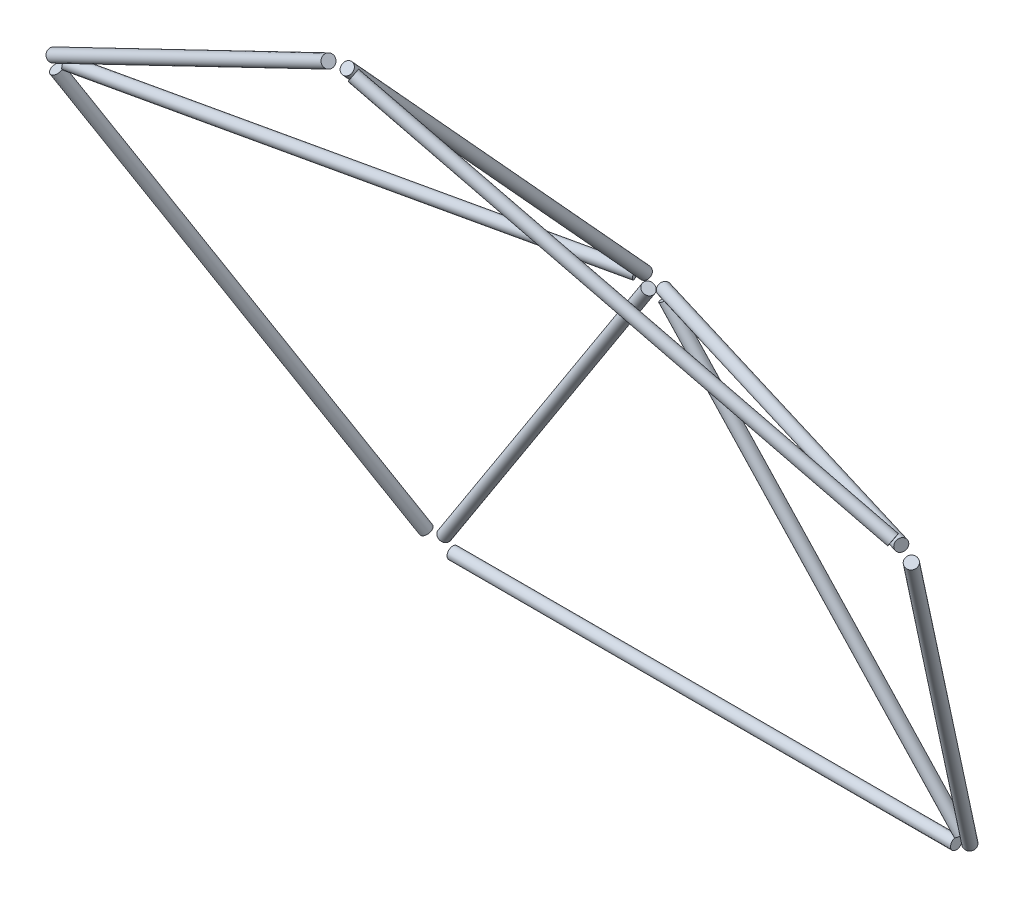
SolidWorks part; units mm, degrees
note: '?' marks a value the reader was unsure of.
ref_plane "Front Plane" through (0, 0, 0) normal (0, 0, 1) x (1, 0, 0)
ref_plane "Top Plane" through (0, 0, 0) normal (0, 1, 0) x (1, 0, 0)
ref_plane "Right Plane" through (0, 0, 0) normal (1, 0, 0) x (0, 0, -1)
sketch "Sketch1" plane through (0, 0, 0) normal (0, 1, 0) x (1, 0, 0)
  line L0 (178.7928, 134.6028) -> (72.7649, 211.6366)
  line L1 (182.0288, -132.2517) -> (225, 0) construction
  line L2 (225, 0) -> (182.0288, 132.2517) construction
  line L3 (182.0288, 132.2517) -> (69.5288, 213.9877) construction
  line L4 (69.5288, 213.9877) -> (-69.5288, 213.9877) construction
  line L5 (-69.5288, 213.9877) -> (-182.0288, 132.2517) construction
  line L6 (-182.0288, 132.2517) -> (-225, 0) construction
  line L7 (-225, 0) -> (-182.0288, -132.2517) construction
  line L8 (-182.0288, -132.2517) -> (-69.5288, -213.9877) construction
  line L9 (-69.5288, -213.9877) -> (69.5288, -213.9877) construction
  line L10 (69.5288, -213.9877) -> (182.0288, -132.2517) construction
  line L11 (112.5, 81.736) -> (69.5288, 213.9877) construction
  line L12 (69.5288, 213.9877) -> (-69.5288, 213.9877) construction
  line L13 (-69.5288, 213.9877) -> (-112.5, 81.736) construction
  line L14 (-112.5, 81.736) -> (0, 0) construction
  line L15 (0, 0) -> (112.5, 81.736) construction
  line L16 (0, 0) -> (-182.0288, -132.2517) construction
  line L17 (-69.5288, -213.9877) -> (69.5288, 213.9877) construction
  circle A0 centre (0, 0) radius 225 construction
  circle A1 centre (0, 0) radius 213.9877 construction
  circle A2 centre (0, 118.2895) radius 95.6982 construction
  point P16 (0, 225)
  point P24 (0, 213.9877)
  dimension "D1" = 450
  dimension "D2" = 4
  dimension "D3" = 4
sketch "Sketch5" plane through (0, 0, 0) normal (1, 0, 0) x (0, 0, -1)
  line L0 (0, 0) -> (118.2895, 191.3964)
  line L1 (118.2895, 191.3964) -> (213.9877, 0)
  line L2 (171.1902, 85.5951) -> (201.2461, 100.6231) construction
  line L3 (-49.7754, 154.1978) -> (144.5877, 34.0748) construction
  circle A0 centre (213.9877, 0) radius 213.9877 construction
  circle A1 centre (0, 0) radius 225 construction
  circle A2 centre (213.9877, 0) radius 95.6982 construction
  point P0 (213.9877, 0)
  point P8 (118.2895, 191.3964)
ref_plane "Plane1" through (0, 85.5951, -171.1902) normal (0, 0.4472, -0.8944) x (-1, 0, 0)
sketch "Sketch6" plane through (0, 85.5951, -171.1902) normal (0, 0.4472, -0.8944) x (-1, 0, 0)
  line L0 (-69.5288, -95.6982) -> (69.5288, -95.6982) construction
  line L1 (-69.5288, -95.6982) -> (69.5288, -95.6982)
  line L2 (-111.2639, 32.7492) -> (-70.7649, -91.894)
  line L3 (-69.5288, -95.6982) -> (69.5288, -95.6982)
  line L4 (69.5288, -95.6982) -> (112.5, 36.5535)
  line L5 (112.5, 36.5535) -> (0, 118.2895)
  line L6 (0, 118.2895) -> (-112.5, 36.5535)
  line L7 (-112.5, 36.5535) -> (-69.5288, -95.6982) construction
  circle A0 centre (0, 0) radius 95.6982 construction
  point P0 (0, 0)
  dimension "D1" = 4
  dimension "D2" = 4
ref_plane "Plane2" through (0, 100.6231, -201.2461) normal (0, 0.4472, -0.8944) x (-1, 0, 0)
sketch "Sketch7" plane through (0, 100.6231, -201.2461) normal (0, 0.4472, -0.8944) x (-1, 0, 0)
  point P0 (0, 0)
ref_plane "Plane7" through (41.3416, 140.4726, -153.7089) normal (0.1947, 0.6617, -0.724) x (-0.9809, 0.1314, -0.1438)
sketch "Sketch15" plane through (41.3416, 140.4726, -153.7089) normal (0.1947, 0.6617, -0.724) x (-0.9809, 0.1314, -0.1438)
  line L0 (-72.5473, -17.1401) -> (42.1485, -61.485)
  line L1 (42.1485, -61.485) -> (42.1485, 61.485)
  line L2 (42.1485, 61.485) -> (-72.5473, -17.1401)
surface "Surface-Plane1" sketch "Sketch15"
ref_plane "Plane8" through (66.8921, 70.1381, -188.8761) normal (0.3151, 0.3304, -0.8897) x (-0.9491, 0.1097, -0.2954)
sketch "Sketch16" plane through (66.8921, 70.1381, -188.8761) normal (0.3151, 0.3304, -0.8897) x (-0.9491, 0.1097, -0.2954)
  line L0 (-2.7783, -74.4928) -> (70.4824, 24.2719) construction
  line L1 (68.0994, 21.0593) -> (-0.3952, -71.2802)
  dimension "D1" = 4
  dimension "D2" = 4
ref_axis "Axis2" through (0, 85.5951, -171.1902) along (0, 0.4472, -0.8944)?
ref_axis "Axis3" through (0, -137.2552, 0) along (0, 1, 0)?
pattern_circular "CirPattern4" count 5 over 360 about axis through (0, 85.5951, -171.1902) along (0, 0.4472, -0.8944)
pattern_circular "CirPattern5" count 5 over 360 about axis through (0, 0, 0) along (0, 1, 0)
ref_plane "Plane11" through (121.3525, 39.4298, -167.0275) normal (0.5774, 0.1876, -0.7947) x (-0.8165, 0.1326, -0.5619)
pattern_circular "CirPattern6" [suppressed] count 5 over 360 about axis through (0, -137.2552, 0) along (0, 1, 0)
ref_plane "Plane12" through (0, 0, 0) normal (0, -0.5257, -0.8507) x (-1, 0, 0)
mirror "Mirror1" about plane through (0, 0, 0) normal (0, -0.5257, -0.8507)
ref_axis "Axis1" through (0, 107.8975, 0) along (0, -1, 0)?
ref_plane "Plane13" through (2.2617, 97.35, -201.6606) normal (0.5654, -0.8183, -0.1036) x (-0.8248, -0.5609, -0.071)
sketch "Sketch20" plane through (2.2617, 97.35, -201.6606) normal (0.5654, -0.8183, -0.1036) x (-0.8248, -0.5609, -0.071)
  circle A0 centre (0, 0) radius 1.5
  dimension "D1" = 3
sweep "Sweep4" add profiles "Sketch20" path "Sketch16"
ref_plane "Plane14" through (70.7649, 3.4026, -212.2864) normal (-0.309, -0.8507, -0.4253) x (-0.9511, 0.2764, 0.1382)
sketch "Sketch21" plane through (70.7649, 3.4026, -212.2864) normal (-0.309, -0.8507, -0.4253) x (-0.9511, 0.2764, 0.1382)
  circle A0 centre (0, 0) radius 1.5
  dimension "D1" = 3
sweep "Sweep5" add profiles "Sketch21" path "Sketch6"
pattern_circular "CirPattern7" count 5 over 360 about axis through (0, 85.5951, -171.1902) along (0, 0.4472, -0.8944) of bodies 167
pattern_circular "CirPattern8" count 5 over 360 about axis through (0, 0, 0) along (0, 0.4472, -0.8944) of bodies 168
ref_plane "Plane15" through (72.7649, 0, -211.6366) normal (-0.809, 0, -0.5878) x (-0.5878, 0, 0.809)
sketch "Sketch22" plane through (72.7649, 0, -211.6366) normal (-0.809, 0, -0.5878) x (-0.5878, 0, 0.809)
  circle A0 centre (0, 0) radius 1.5
  dimension "D1" = 3
sketch "Sketch23" plane through (0, 0, 0) normal (0, 1, 0) x (1, 0, 0)
  line L0 (-210, 0) -> (-169.8936, -123.4349)
  line L1 (169.8936, -123.4349) -> (210, 0)
  line L2 (210, 0) -> (169.8936, 123.4349)
  line L3 (169.8936, 123.4349) -> (64.8936, 199.7219)
  line L4 (64.8936, 199.7219) -> (-64.8936, 199.7219)
  line L5 (-64.8936, 199.7219) -> (-169.8936, 123.4349)
  line L6 (-169.8936, 123.4349) -> (-210, 0)
  line L7 (-169.8936, -123.4349) -> (-64.8936, -199.7219)
  line L8 (-64.8936, -199.7219) -> (64.8936, -199.7219)
  line L9 (64.8936, -199.7219) -> (169.8936, -123.4349)
  circle A0 centre (0, 0) radius 199.7219 construction
  dimension "D1" = 420
